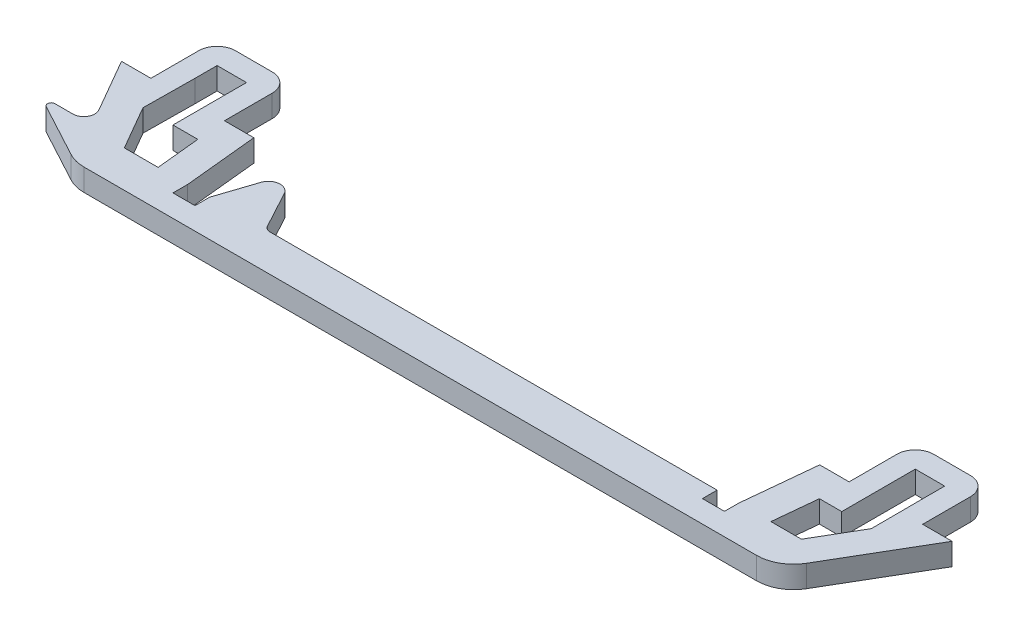
SolidWorks part; units mm, degrees
material "Custom Plastic"
ref_plane "Front Plane" through (0, 0, 0) normal (0, 0, 1) x (1, 0, 0)
ref_plane "Top Plane" through (0, 0, 0) normal (0, 1, 0) x (1, 0, 0)
ref_plane "Right Plane" through (0, 0, 0) normal (1, 0, 0) x (0, 0, -1)
sketch "Sketch1" plane through (0, 0, 0) normal (0, 1, 0) x (1, 0, 0)
  line L0 (-62.4186, -47.1587) -> (-58.4186, -47.1587)
  line L1 (-58.4186, -47.1587) -> (-58.4186, -38.1587)
  line L2 (-58.4186, -38.1587) -> (-48.4186, -38.1587)
  line L3 (-48.4186, -38.1587) -> (-48.4186, -47.1587)
  line L4 (-48.4186, -47.1587) -> (-44.4186, -47.1587)
  line L5 (-44.4186, -47.1587) -> (-43.4188, -57.1562)
  line L7 (31.5814, -57.2088) -> (32.5814, -47.2113)
  line L8 (32.5814, -47.2113) -> (36.5814, -47.2113)
  line L9 (36.5814, -47.2113) -> (36.5814, -38.2113)
  line L10 (36.5814, -38.2113) -> (46.5814, -38.2113)
  line L11 (46.5814, -38.2113) -> (46.5814, -47.2113)
  line L12 (46.5814, -47.2113) -> (50.5814, -47.2113)
  line L13 (50.5814, -47.2113) -> (41.8306, -62.1587)
  line L14 (41.8306, -62.1587) -> (-53.7583, -62.1587)
  line L15 (-58.2259, -54.4205) -> (-62.4186, -47.1587)
  line L16 (36.5478, -51.2113) -> (39.5814, -51.2113)
  line L17 (-55.4186, -41.1587) -> (-51.4186, -41.1587)
  line L18 (-55.4186, -41.1587) -> (-55.4186, -44.1587)
  line L20 (-51.4186, -41.1587) -> (-51.4186, -44.1587)
  line L21 (39.5814, -41.2113) -> (43.5814, -41.2113)
  line L22 (39.5814, -41.2113) -> (39.5814, -44.2113)
  line L24 (43.5814, -41.2113) -> (43.5814, -44.2113)
  line L25 (43.6046, -51.2113) -> (40.0934, -57.2088)
  line L26 (40.0934, -57.2088) -> (35.9479, -57.2088)
  line L27 (35.9479, -57.2088) -> (36.5478, -51.2113)
  line L28 (-51.4186, -51.1587) -> (-48.0385, -51.1587)
  line L29 (-48.0385, -51.1587) -> (-47.4385, -57.1587)
  line L30 (-47.4385, -57.1587) -> (-52.0263, -57.1587)
  line L31 (-52.0263, -57.1587) -> (-55.4904, -51.1587)
  line L32 (28.5814, -57.1587) -> (28.5814, -59.1587)
  line L33 (28.5814, -47.1587) -> (28.5814, -62.1587) construction
  line L34 (28.5814, -59.1587) -> (31.5814, -59.1587)
  line L35 (31.5814, -59.1587) -> (31.5814, -57.2088)
  line L36 (31.5814, -62.1587) -> (31.5814, -47.1587) construction
  line L38 (-43.4188, -57.1562) -> (-43.4188, -59.1587)
  line L39 (-43.4188, -59.1587) -> (-40.4188, -59.1587)
  line L40 (-40.4188, -59.1587) -> (-40.4188, -57.1587)
  line L41 (-32.8035, -57.1587) -> (28.5814, -57.1587)
  line L42 (-32.8035, -57.1587) -> (-35.7725, -51.6685)
  line L43 (43.5814, -44.2113) -> (43.6046, -51.2113)
  line L44 (-38.6829, -51.9246) -> (-40.4188, -57.1587)
  line L45 (39.5814, -44.2113) -> (39.5814, -51.2113)
  line L46 (-55.4186, -44.1587) -> (-55.4904, -51.1587)
  line L47 (-51.4186, -44.1587) -> (-51.4186, -51.1587)
  line L48 (-53.7583, -62.1587) -> (-62.2024, -57.6107)
  line L49 (-61.9653, -56.6705) -> (-59.525, -56.6705)
  arc A0 (-38.6829, -51.9246) -> (-35.7725, -51.6685) centre (-37.1723, -52.4255) cw
  arc A1 (-59.525, -56.6705) -> (-58.2259, -54.4205) centre (-59.525, -55.1705) ccw
  arc A2 (-62.2024, -57.6107) -> (-61.9653, -56.6705) centre (-61.9653, -57.1705) cw
  point P36 (0, 0)
  point P39 (-32.8035, -57.1587)
  point P56 (-34.9133, -51.76)
  point P57 (-36.6519, -52.0902)
  point P58 (-35.7725, -51.9246)
  dimension "D6" = 0.5
  dimension "D5" = 1.5
  dimension "D1" = 15
  dimension "D2" = 4
  dimension "D3" = 9
  dimension "D4" = 3
  dimension "D7" = 120
  dimension "D8" = 10
  dimension "D9" = 85
  dimension "D10" = 3
  dimension "D11" = 95.5889
  dimension "D12" = 3
  dimension "D13" = 3
  dimension "D14" = 3
  dimension "D15" = 3
  dimension "D17" = 4
  dimension "D18" = 4
  dimension "D19" = 4
  dimension "D20" = 4
  dimension "D21" = 4
  dimension "D23" = 2
  dimension "D24" = 3
extrude "Boss-Extrude1" add sketch "Sketch1" along normal blind 3
fillet "Fillet1" radius 5 2 edges at (41.8306, 1.5, 62.1587) (-53.7583, 1.5, 62.1587)
fillet "Fillet2" radius 2.5 4 edges at (46.5814, 1.5, 38.2113) (36.5814, 1.5, 38.2113) (-58.4186, 1.5, 38.1587) (-48.4186, 1.5, 38.1587)
fillet "Fillet3" radius 1 1 edges at (-32.8035, 1.5, 57.1587)
